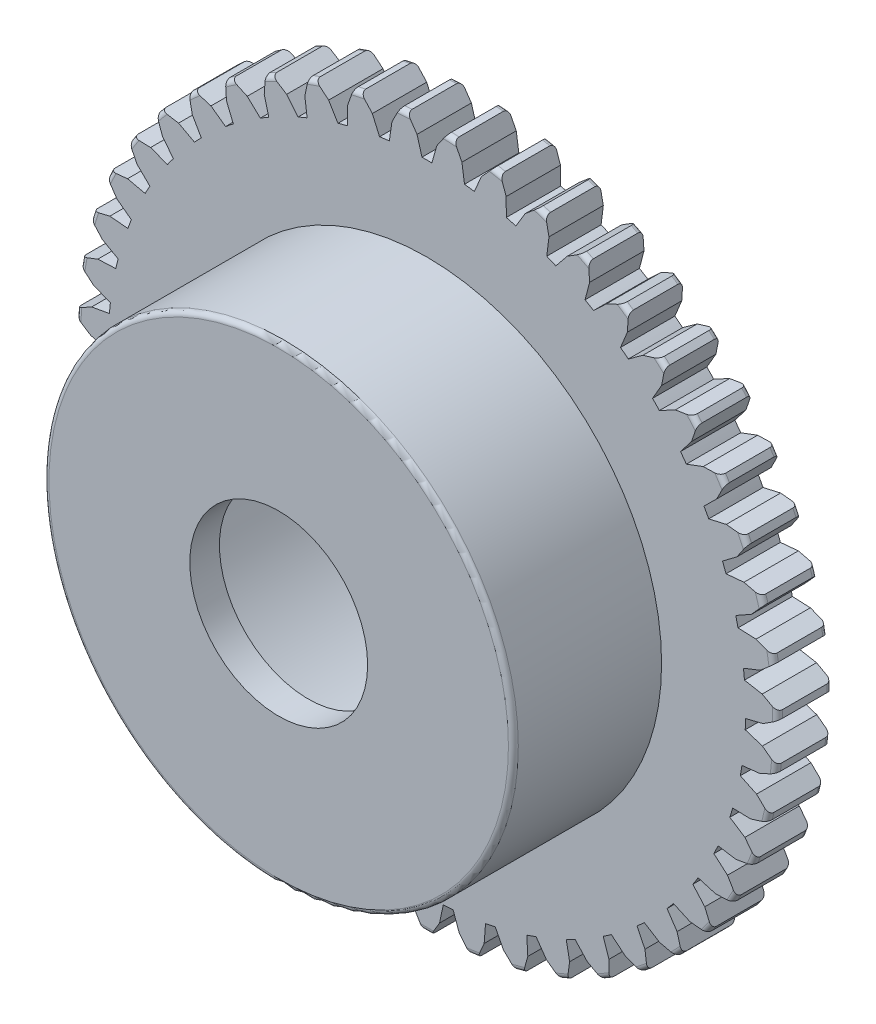
SolidWorks part; units mm, degrees
material "Latón de decoletaje, UNS C36000"
ref_plane "Alzado" through (0, 0, 0) normal (0, 0, 1) x (1, 0, 0)
ref_plane "Planta" through (0, 0, 0) normal (0, 1, 0) x (1, 0, 0)
ref_plane "Vista lateral" through (0, 0, 0) normal (1, 0, 0) x (0, 0, -1)
sketch "Croquis1" plane through (0, 0, 0) normal (0, 0, 1) x (1, 0, 0)
  circle A0 centre (0, 0) radius 7.1
  circle A1 centre (0, 0) radius 4
  dimension "D1" = 14.2
  dimension "D2" = 8
extrude "Saliente-Extruir1" add sketch "Croquis1" along normal blind 1.1
sketch "Croquis2" plane through (0, 0, 1.1) normal (0, 0, 1) x (1, 0, 0)
  line L0 (0, 0) -> (0, 11.5202) construction
  line L1 (0.4, 7.2029) -> (-0.4, 7.2029)
  line L2 (-0.4, 7.2029) -> (-0.4, 7.0887)
  line L3 (-0.4, 7.0887) -> (-0.2, 6.8)
  line L4 (-0.2, 6.8) -> (-0.1, 6.4492)
  line L5 (0.2, 6.8) -> (0.1, 6.4492)
  line L6 (0.4, 7.2029) -> (0.4, 7.0887)
  line L7 (0.4, 7.0887) -> (0.2, 6.8)
  circle A0 centre (0, 0) radius 6.45
  circle A1 centre (0, 0) radius 7.1 construction
  circle A2 centre (0, 0) radius 1.8
  point P15 (0, 7.2029)
  circle M6 centre (0, 0) radius 7.1
  dimension "D1" = 12.9
  dimension "D7" = 3.6
  dimension "D2" = 0.4
  dimension "D3" = 0.1
  dimension "D4" = 0.2
  dimension "D5" = 6.8
  dimension "D6" = 7.2029
extrude "Cortar-Extruir1" cut sketch "Croquis2" against normal blind 1.1 contours A0 L0 L3 L4 M6 | L0 A0 L5 L7 M6 | L0 L6 L1 M6 | L0 L1 L2 M6 region at (-0.1267, 6.8464, 1.1) region at (0.1267, 6.8464, 1.1) region at (-0.2035, 7.1495, 1.1) region at (0.2035, 7.1495, 1.1)
fillet "Redondeo2" radius 0.1 2 edges at (0, -7.1, 0) (0, -7.1, 1.1)
pattern_circular "MatrizC1" count 47 over 360 about axis through (0, 0, 1.1) along (0, 0, -1) of "Cortar-Extruir1"
sketch "Croquis4" plane through (0, 0, 1.1) normal (0, 0, 1) x (1, 0, 0)
  circle A0 centre (0, 0) radius 4.75
  dimension "D1" = 9.5
extrude "Saliente-Extruir2" add sketch "Croquis4" along normal blind 3
fillet "Redondeo3" radius 0.1 1 edges at (4.75, 0, 4.1)
sketch "Croquis5" plane through (0, 0, 0) normal (0, 0, -1) x (-1, 0, 0)
extrude "Cortar-Extruir3" cut sketch "Croquis2<6>" along normal blind 4.5 contours A2 region at (0, 0, 1.1)
sketch "Croquis2<6>" plane through (0, 0, 1.1) normal (0, 0, 1) x (1, 0, 0) same geometry as "Croquis2"
extrude "Cortar-Extruir4" cut sketch "Croquis1<4>" along normal blind 3.5 contours A1 region at (0, 0, 0)
sketch "Croquis1<4>" plane through (0, 0, 0) normal (0, 0, 1) x (1, 0, 0) same geometry as "Croquis1"
